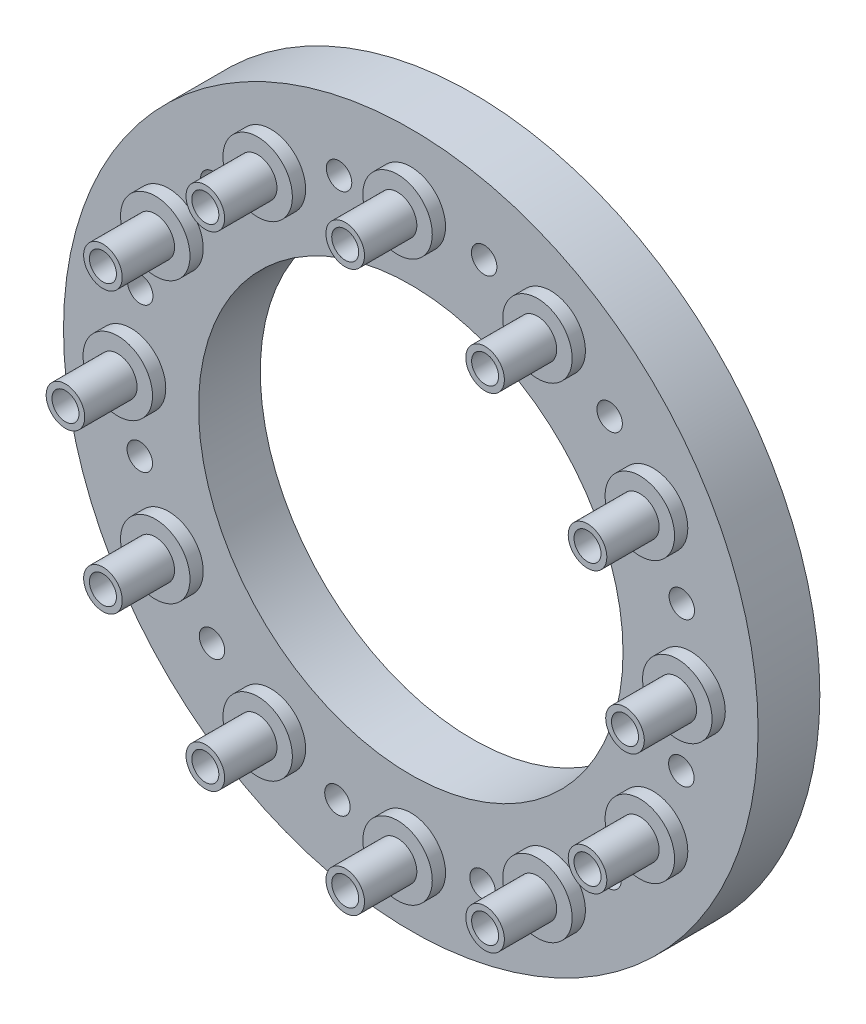
SolidWorks part; units mm, degrees
ref_plane "Front Plane" through (0, 0, 0) normal (0, 0, 1) x (1, 0, 0)
ref_plane "Top Plane" through (0, 0, 0) normal (0, 1, 0) x (1, 0, 0)
ref_plane "Right Plane" through (0, 0, 0) normal (1, 0, 0) x (0, 0, -1)
sketch "Sketch1" plane through (0, 0, 0) normal (0, 0, 1) x (1, 0, 0)
  circle A0 centre (0, 0) radius 180
  circle A1 centre (0, 0) radius 110
extrude "Bottom Annulus" add sketch "Sketch1" along normal blind 10
sketch "Sketch3" plane through (0, 0, 10) normal (0, 0, 1) x (1, 0, 0)
  circle A0 centre (0, 0) radius 180
  circle A2 centre (0, 0) radius 110
extrude "Annulus Plenum" add sketch "Sketch3" along normal blind 12
sketch "Sketch4" plane through (0, 0, 22) normal (0, 0, 1) x (1, 0, 0)
  circle A0 centre (0, 0) radius 110
  circle A1 centre (0, 0) radius 180
extrude "Top annulus" add sketch "Sketch4" along normal blind 10
sketch "Sketch2" plane through (0, 0, 0) normal (0, 0, 1) x (1, 0, 0)
  circle A0 centre (0, 0) radius 120
sketch "Sketch6" plane through (0, 0, 32) normal (0, 0, 1) x (1, 0, 0)
  line L0 (0, 180) -> (0, 110) construction
  circle A0 centre (0, 0) radius 180 construction
  circle A1 centre (0, 0) radius 110 construction
  circle A2 centre (0, 145) radius 18
  circle A3 centre (0, 145) radius 10
  circle A4 centre (72.5, 125.5737) radius 18
  circle A5 centre (72.5, 125.5737) radius 10
  circle A6 centre (125.5737, 72.5) radius 18
  circle A7 centre (125.5737, 72.5) radius 10
  circle A8 centre (145, 0) radius 18
  circle A9 centre (145, 0) radius 10
  circle A10 centre (125.5737, -72.5) radius 18
  circle A11 centre (125.5737, -72.5) radius 10
  circle A12 centre (72.5, -125.5737) radius 18
  circle A13 centre (72.5, -125.5737) radius 10
  circle A14 centre (0, -145) radius 18
  circle A15 centre (0, -145) radius 10
  circle A16 centre (-72.5, -125.5737) radius 18
  circle A17 centre (-72.5, -125.5737) radius 10
  circle A18 centre (-125.5737, -72.5) radius 18
  circle A19 centre (-125.5737, -72.5) radius 10
  circle A20 centre (-145, 0) radius 18
  circle A21 centre (-145, 0) radius 10
  circle A22 centre (-125.5737, 72.5) radius 18
  circle A23 centre (-125.5737, 72.5) radius 10
  circle A24 centre (-72.5, 125.5737) radius 18
  circle A25 centre (-72.5, 125.5737) radius 10
  point P46 (0, 0)
  dimension "D1" = 12
sketch "Sketch8" plane through (0, 0, 32) normal (0, 0, 1) x (1, 0, 0)
  line L0 (0, 0) -> (-46.0641, 174.006) construction
  circle A0 centre (0, 0) radius 180 construction
  circle A1 centre (-37.1811, 140.4506) radius 6.6
  circle A2 centre (38.0255, 140.2244) radius 6.6
  circle A3 centre (103.0433, 102.4251) radius 6.6
  circle A4 centre (140.4506, 37.1811) radius 6.6
  circle A5 centre (140.2244, -38.0255) radius 6.6
  circle A6 centre (102.4251, -103.0433) radius 6.6
  circle A7 centre (37.1811, -140.4506) radius 6.6
  circle A8 centre (-38.0255, -140.2244) radius 6.6
  circle A9 centre (-103.0433, -102.4251) radius 6.6
  circle A10 centre (-140.4506, -37.1811) radius 6.6
  circle A11 centre (-140.2244, 38.0255) radius 6.6
  circle A12 centre (-102.4251, 103.0433) radius 6.6
  point P7 (0, 0)
  point P8 (0, 0)
  point P9 (0, 0)
  point P32 (0, 0)
  point P33 (0, 0)
  point P34 (-37.1811, 140.2244)
  dimension "D1" = 12
extrude "Cut-Extrude1" cut sketch "Sketch8" against normal blind 75
extrude "Boss-Extrude6" add sketch "Sketch6" along normal blind 6.8712
sketch "Sketch10" plane through (0, 0, 32) normal (0, 0, 1) x (1, 0, 0)
  circle A0 centre (0, 145) radius 10
  circle A1 centre (72.5, 125.5737) radius 10
  circle A2 centre (125.5737, 72.5) radius 10
  circle A3 centre (145, 0) radius 10
  circle A4 centre (125.5737, -72.5) radius 10
  circle A5 centre (72.5, -125.5737) radius 10
  circle A6 centre (0, -145) radius 10
  circle A7 centre (-72.5, -125.5737) radius 10
  circle A8 centre (-125.5737, -72.5) radius 10
  circle A9 centre (-145, 0) radius 10
  circle A10 centre (-125.5737, 72.5) radius 10
  circle A11 centre (-72.5, 125.5737) radius 10
  circle A12 centre (0, 145) radius 7
  circle A13 centre (72.5, 125.5737) radius 7
  circle A14 centre (125.5737, 72.5) radius 7
  circle A15 centre (145, 0) radius 7
  circle A16 centre (125.5737, -72.5) radius 7
  circle A17 centre (72.5, -125.5737) radius 7
  circle A18 centre (0, -145) radius 7
  circle A19 centre (-72.5, -125.5737) radius 7
  circle A20 centre (-125.5737, -72.5) radius 7
  circle A21 centre (-145, 0) radius 7
  circle A22 centre (-125.5737, 72.5) radius 7
  circle A23 centre (-72.5, 125.5737) radius 7
  point P27 (0, 0)
  point P51 (0, 0)
  dimension "D2" = 12
  dimension "D1" = 12
extrude "Boss-Extrude7" add sketch "Sketch10" along normal blind 33.9893
sketch3d "3DSketch1"
  line L0 (0, -0.0876, 16.064) -> (0, 15.8787, 16.064)
  line L1 (0, 15.8787, 16.064) -> (0, 16.1362, 19.1543)
  line L2 (0, 16.1362, 19.1543) -> (0, -0.3451, 19.1543)
  line L3 (0, -0.3451, 19.1543) -> (0, -0.0876, 16.064)
  circle A0 centre (0, 0, 0) radius 120 construction
  circle A1 centre (0, 0, 0) radius 120
  point P2 (0, 0, 120)
  point P4 (0, 0, 120)
ref_axis "Axis1" through (0, 0, 69.2888) along (0, 0, -1)
